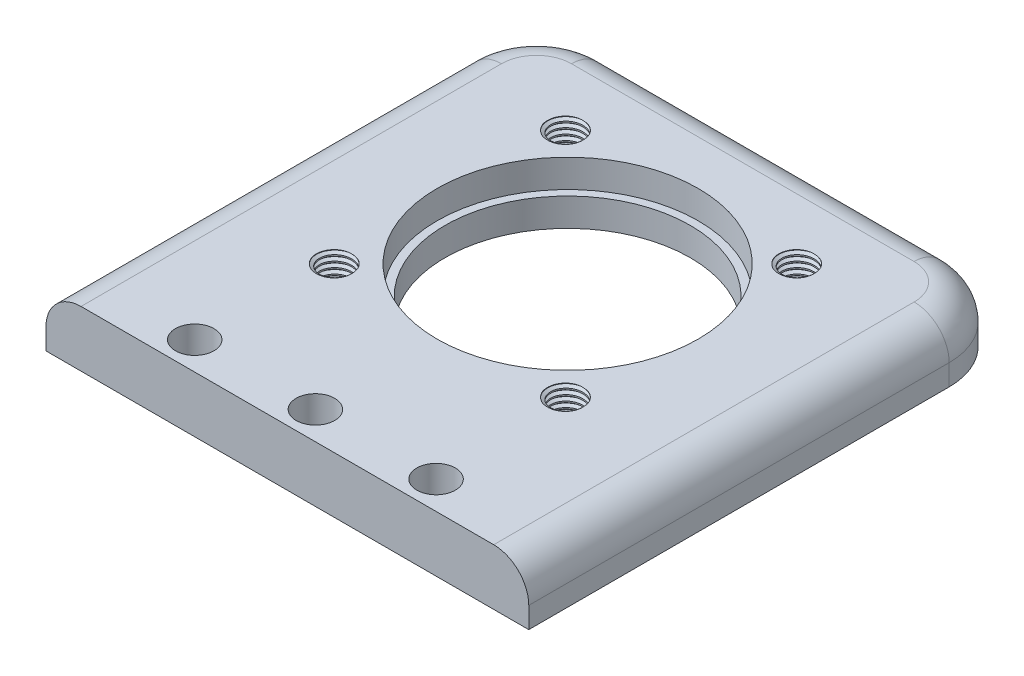
SolidWorks part; units mm, degrees
ref_plane "Front Plane" through (0, 0, 0) normal (0, 0, 1) x (1, 0, 0)
ref_plane "Top Plane" through (0, 0, 0) normal (0, 1, 0) x (1, 0, 0)
ref_plane "Right Plane" through (0, 0, 0) normal (1, 0, 0) x (0, 0, -1)
sketch "Sketch1" plane through (0, 0, 0) normal (0, 1, 0) x (1, 0, 0)
  line L1 (0, 0) -> (68.9, 0)
  line L2 (0, 0) -> (0, 70)
  line L3 (0, 70) -> (68.9, 70)
  line L4 (68.9, 0) -> (68.9, 70)
  circle A0 centre (34.45, 40) radius 18.63
  circle A1 centre (34.45, 4) radius 2.75
  circle A2 centre (17.225, 4) radius 2.75
  circle A3 centre (51.675, 4) radius 2.75
  dimension "D3" = 34.45
  dimension "D5" = 34.45
  dimension "D8" = 4
  dimension "D1" = 68.9
  dimension "D2" = 70
  dimension "D4" = 30
  dimension "D6" = 17.225
  dimension "D7" = 17.225
extrude "Boss-Extrude1" add sketch "Sketch1" along normal blind 8
fillet "Fillet1" radius 10 2 edges at (68.9, 4, -70) (0, 4, -70)
fillet "Fillet2" radius 5 5 edges at (65.9711, 8, -67.0711) (34.45, 8, -70) (2.9289, 8, -67.0711) (68.9, 8, -30) (0, 8, -30)
sketch "Sketch2" plane through (0, 0, 0) normal (0, -1, 0) x (1, 0, 0)
  circle A0 centre (34.45, -40) radius 18.63
  circle A1 centre (34.45, -40) radius 17.5
extrude "Boss-Extrude2" add sketch "Sketch2" against normal blind 4
sketch "Sketch5" plane through (0, 8, 0) normal (0, 1, 0) x (1, 0, 0)
  line L1 (50.95, 23.5) -> (17.95, 23.5)
  line L2 (50.95, 23.5) -> (50.95, 56.5)
  line L3 (50.95, 56.5) -> (17.95, 56.5)
  line L4 (17.95, 23.5) -> (17.95, 56.5)
  line L5 (50.95, 23.5) -> (17.95, 56.5) construction
  line L6 (50.95, 56.5) -> (17.95, 23.5) construction
  circle A0 centre (17.95, 56.5) radius 2.3
  circle A1 centre (50.95, 56.5) radius 2.3
  circle A2 centre (50.95, 23.5) radius 2.3
  circle A3 centre (17.95, 23.5) radius 2.3
  point P0 (34.45, 40)
  dimension "D1" = 33
  dimension "D2" = 33
extrude "Cut-Extrude1" cut sketch "Sketch5" against normal blind 6 contours L3 A0 L4 | L4 A0 L3 | L2 A1 L3 | L1 A2 L2 | L4 A3 L1 | L1 A3 L4 | L2 A2 L1 region at (17.6246, 8, -23.1746) region at (18.9262, 8, -24.4762) region at (49.9738, 8, -24.4762) region at (51.2754, 8, -23.1746) region at (17.6246, 8, -56.8254) region at (18.9262, 8, -55.5238) region at (51.2754, 8, -56.8254)
thread "Thread1" pitch 0.8 method cut profile "Thread Profile1" start angle 0, offset 1, length 0, pitch 0.8, diameter 4.6
ref_plane "Plane1" through (15.65, 9, -56.5) normal (0, 0, 1) x (-1, 0, 0)
sketch "Thread Profile1" plane through (15.65, 9, -56.5) normal (0, 0, 1) x (-1, 0, 0)
  line L0 (0, 0) -> (0, 0.8) construction
  line L1 (0, 0) -> (0.433, 0.25)
  line L2 (0.433, 0.25) -> (0.433, 0.35)
  line L3 (0.433, 0.35) -> (0, 0.6)
  line L4 (0.433, 0.3) -> (0, 0.3) construction
  line L11 (0, 0) -> (0, 0.6)
  point P2 (0, 0)
  dimension "Pitch" = 0.8
  dimension "Profile_Angle" = 60
  dimension "Profile_Land" = 0.1
  dimension "Profile_Height" = 0.433
thread "Thread2" pitch 0.8 method cut profile "Thread Profile2" start angle 0, offset 1, length 0, pitch 0.8, diameter 4.6
ref_plane "Plane2" through (48.65, 9, -23.5) normal (0, 0, 1) x (-1, 0, 0)
sketch "Thread Profile2" plane through (48.65, 9, -23.5) normal (0, 0, 1) x (-1, 0, 0)
  line L0 (0, 0) -> (0, 0.8) construction
  line L1 (0, 0) -> (0.433, 0.25)
  line L2 (0.433, 0.25) -> (0.433, 0.35)
  line L3 (0.433, 0.35) -> (0, 0.6)
  line L4 (0.433, 0.3) -> (0, 0.3) construction
  line L11 (0, 0) -> (0, 0.6)
  point P2 (0, 0)
  dimension "Pitch" = 0.8
  dimension "Profile_Angle" = 60
  dimension "Profile_Land" = 0.1
  dimension "Profile_Height" = 0.433
thread "Thread3" pitch 0.8 method cut profile "Thread Profile3" start angle 0, offset 1, length 0, pitch 0.8, diameter 4.6
ref_plane "Plane3" through (15.65, 9, -23.5) normal (0, 0, 1) x (-1, 0, 0)
sketch "Thread Profile3" plane through (15.65, 9, -23.5) normal (0, 0, 1) x (-1, 0, 0)
  line L0 (0, 0) -> (0, 0.8) construction
  line L1 (0, 0) -> (0.433, 0.25)
  line L2 (0.433, 0.25) -> (0.433, 0.35)
  line L3 (0.433, 0.35) -> (0, 0.6)
  line L4 (0.433, 0.3) -> (0, 0.3) construction
  line L11 (0, 0) -> (0, 0.6)
  point P2 (0, 0)
  dimension "Pitch" = 0.8
  dimension "Profile_Angle" = 60
  dimension "Profile_Land" = 0.1
  dimension "Profile_Height" = 0.433
extrude "Cut-Extrude2" cut sketch "Sketch5<3>" against normal blind 6 contours L3 A1 L2 region at (49.9738, 8, -55.5238)
sketch "Sketch5<3>" plane through (0, 8, 0) normal (0, 1, 0) x (1, 0, 0) same geometry as "Sketch5"
thread "Thread4" pitch 0.8 method cut profile "Thread Profile4" start angle 0, offset 1, length 0, pitch 0.8, diameter 4.6
ref_plane "Plane4" through (48.65, 9, -56.5) normal (0, 0, 1) x (-1, 0, 0)
sketch "Thread Profile4" plane through (48.65, 9, -56.5) normal (0, 0, 1) x (-1, 0, 0)
  line L0 (0, 0) -> (0, 0.8) construction
  line L1 (0, 0) -> (0.433, 0.25)
  line L2 (0.433, 0.25) -> (0.433, 0.35)
  line L3 (0.433, 0.35) -> (0, 0.6)
  line L4 (0.433, 0.3) -> (0, 0.3) construction
  line L11 (0, 0) -> (0, 0.6)
  point P2 (0, 0)
  dimension "Pitch" = 0.8
  dimension "Profile_Angle" = 60
  dimension "Profile_Land" = 0.1
  dimension "Profile_Height" = 0.433
sketch "Sketch14" plane through (0, 8, 0) normal (0, 1, 0) x (1, 0, 0)
  circle A0 centre (34.45, 40) radius 23.3345
